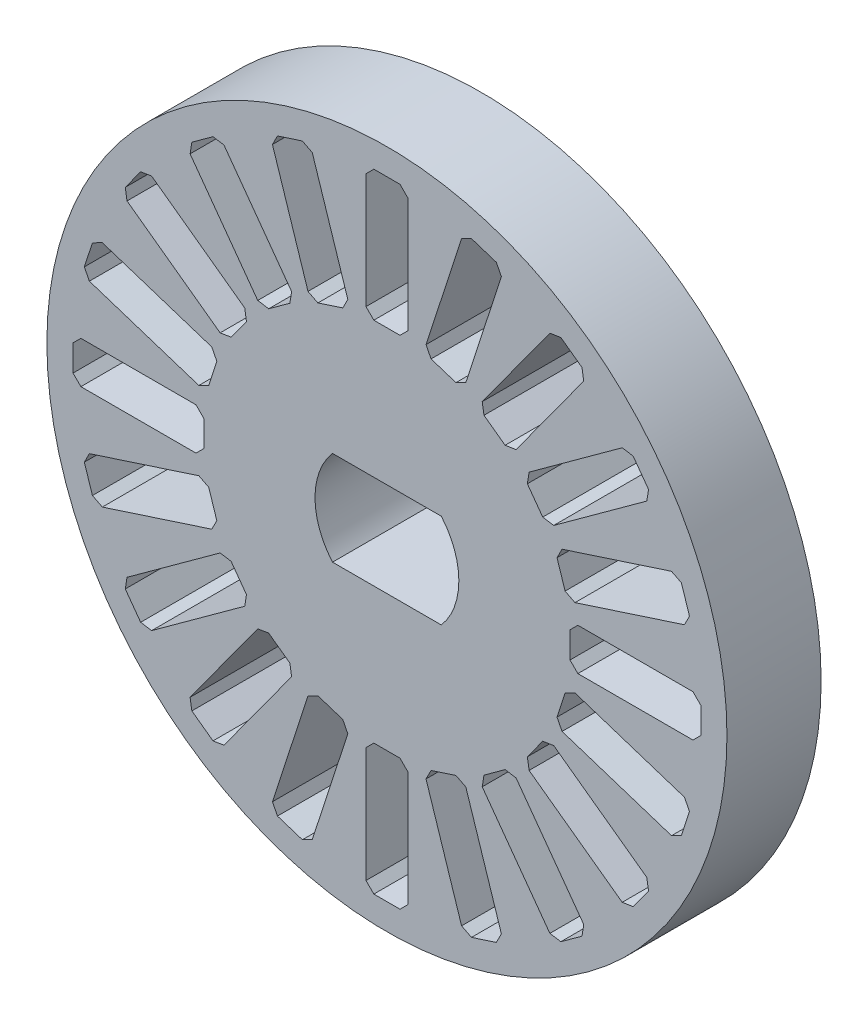
SolidWorks part; units mm, degrees
ref_plane "Спереди" through (0, 0, 0) normal (0, 0, 1) x (1, 0, 0)
ref_plane "Сверху" through (0, 0, 0) normal (0, 1, 0) x (1, 0, 0)
ref_plane "Справа" through (0, 0, 0) normal (1, 0, 0) x (0, 0, -1)
sketch "Эскиз1" plane through (0, 0, 0) normal (0, 0, 1) x (1, 0, 0)
  line L0 (0, 1.8) -> (0, -1.8) construction
  line L1 (-2.0791, 1.8) -> (2.0791, 1.8)
  line L3 (-2.0791, -1.8) -> (2.0791, -1.8)
  arc A0 (-2.0791, 1.8) -> (-2.0791, -1.8) centre (0, 0) ccw
  arc A1 (2.0791, -1.8) -> (2.0791, 1.8) centre (0, 0) ccw
  circle A2 centre (0, 0) radius 13
  point P9 (0, 0)
  dimension "D1" = 5.5
  dimension "D3" = 26
  dimension "D2" = 3.6
extrude "Бобышка-Вытянуть1" add sketch "Эскиз1" along normal blind 3.6
sketch "Эскиз2" plane through (0, 0, 0) normal (0, 0, 1) x (1, 0, 0)
  line L0 (0, 0) -> (-13, 0) construction
  line L2 (-12, 0.8) -> (-7, 0.8)
  line L3 (-12, 0.8) -> (-12, -0.8)
  line L4 (-12, -0.8) -> (-7, -0.8)
  line L5 (-7, 0.8) -> (-7, -0.8)
  circle A0 centre (0, 0) radius 13 construction
  point P10 (-7, 0)
  dimension "D1" = 1
  dimension "D2" = 5
  dimension "D3" = 1.6
extrude "Вырез-Вытянуть2" cut sketch "Эскиз2" along normal through all
chamfer "Фаска1" distance 0.3 angle 45 4 edges at (-7, -0.8, 1.8) (-7, 0.8, 1.8) (-12, 0.8, 1.8) (-12, -0.8, 1.8)
ref_axis "Ось1" through (0, 0, -80.9) along (0, 0, 1)
pattern_circular "Круговой массив1" count 20 over 360 about axis through (0, 0, -80.9) along (0, 0, 1) of "Вырез-Вытянуть2", "Фаска1"
